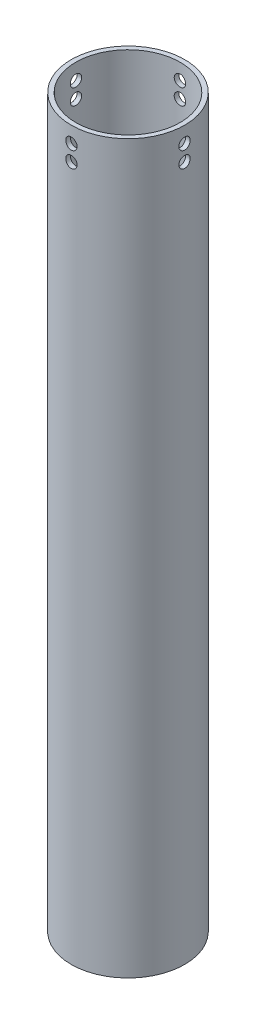
SolidWorks part; units mm, degrees
material "ПВХ 0.007 Смягченный"
ref_plane "Спереди" through (0, 0, 0) normal (0, 0, 1) x (1, 0, 0)
ref_plane "Сверху" through (0, 0, 0) normal (0, 1, 0) x (1, 0, 0)
ref_plane "Справа" through (0, 0, 0) normal (1, 0, 0) x (0, 0, -1)
sketch "Эскиз1" plane through (0, 0, 0) normal (0, 1, 0) x (1, 0, 0)
  circle A0 centre (0, 0) radius 25
  circle A1 centre (0, 0) radius 23
  dimension "ExDBody" = 50
  dimension "InDBody" = 46
extrude "Бобышка-Вытянуть1" add sketch "Эскиз1" along normal blind 320
sketch "Эскиз2" plane through (0, 0, 0) normal (1, 0, 0) x (0, 0, -1)
  line L0 (23, 320) -> (-23, 320) construction
  circle A0 centre (0, 313) radius 2.5
  circle A1 centre (0, 306) radius 2.5
  dimension "D1" = 7
  dimension "D2" = 2
extrude "Вырез-Вытянуть1" cut sketch "Эскиз2" against normal through all
pattern_circular "Круговой массив1" count 4 over 360 about axis through (0, 320, 0) along (0, -1, 0) of "Вырез-Вытянуть1"
